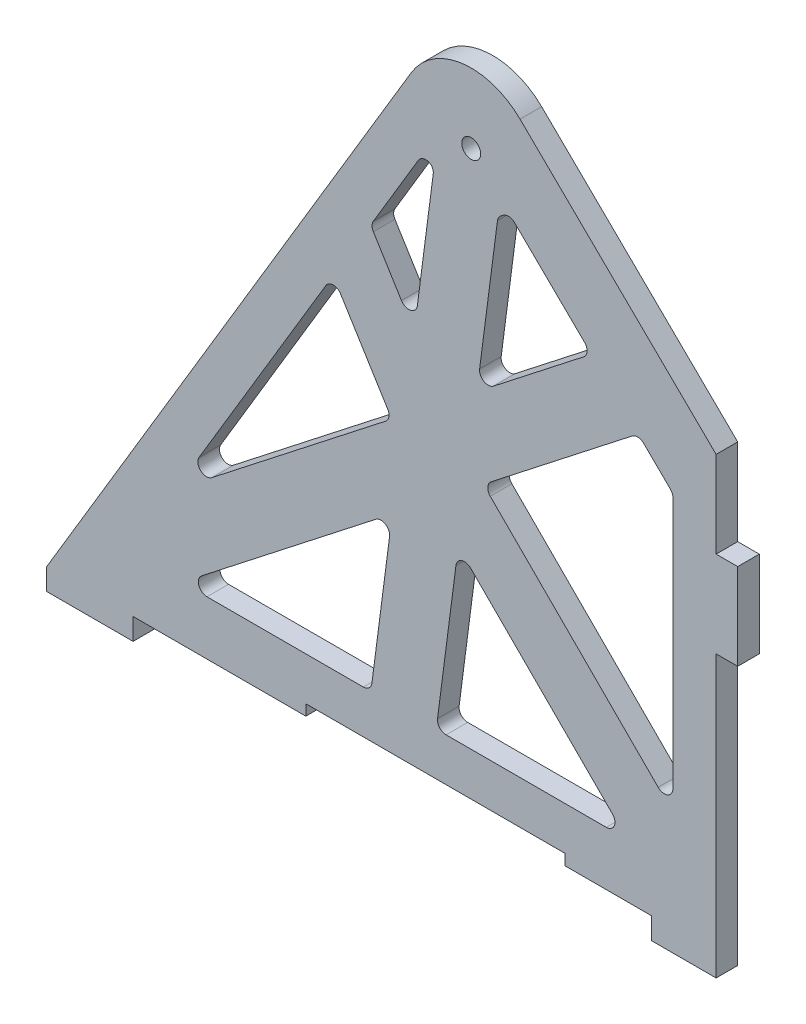
SolidWorks part; units mm, degrees
ref_plane "Front Plane" through (0, 0, 0) normal (0, 0, 1) x (1, 0, 0)
ref_plane "Top Plane" through (0, 0, 0) normal (0, 1, 0) x (1, 0, 0)
ref_plane "Right Plane" through (0, 0, 0) normal (1, 0, 0) x (0, 0, -1)
sketch "Sketch2" plane through (0, 0, 0) normal (0, 0, 1) x (1, 0, 0)
  line L0 (0, 2.5421) -> (203.2, 2.5421) construction
  line L1 (25.4, 2.5421) -> (76.2, 2.5421)
  line L2 (0, 2.5421) -> (107.2144, 181.9515)
  line L4 (76.2, 2.5421) -> (76.2, 5.7171)
  line L6 (0, 2.5421) -> (0, -3.8079)
  line L7 (0, -3.8079) -> (25.4, -3.8079)
  line L8 (25.4, 2.5421) -> (25.4, -3.8079)
  line L13 (76.2, 5.7171) -> (152.4, 5.7171)
  line L14 (152.4, 5.7171) -> (152.4, 2.5421)
  line L16 (152.4, 2.5421) -> (177.8, 2.5421)
  line L17 (0, -33.6061) -> (203.2, -33.6061) construction
  line L18 (177.8, 2.5421) -> (177.8, -3.8079)
  line L19 (177.8, -3.8079) -> (196.85, -3.8079)
  line L20 (196.85, -3.8079) -> (196.85, 78.7421)
  line L22 (196.85, 129.5421) -> (139.2046, 186.0765)
  line L23 (196.85, 104.1421) -> (196.85, 129.5421)
  line L24 (196.85, 104.1421) -> (203.2, 104.1421)
  line L26 (196.85, 78.7421) -> (203.2, 78.7421)
  line L27 (203.2, 104.1421) -> (203.2, 78.7421)
  arc A0 (139.2046, 186.0765) -> (107.2144, 181.9515) centre (124.8331, 171.4226) ccw
  circle A1 centre (124.8331, 171.4226) radius 11 construction
  circle A2 centre (124.8331, 171.4226) radius 4 construction
  circle A3 centre (124.8331, 171.4226) radius 2.7781
  dimension "D3" = 22
  dimension "D4" = 9.525
  dimension "D5" = 8
  dimension "D6" = 5.5562
  dimension "D1" = 168.8805
  dimension "D2" = 124.8331
  dimension "D7" = 6.35
  dimension "D8" = 25.4
  dimension "D9" = 19.05
  dimension "D10" = 6.35
  dimension "D11" = 44.45
  dimension "D12" = 203.2
  dimension "D13" = 76.2
  dimension "D14" = 3.175
  dimension "D15" = 133.35
  dimension "D16" = 6.35
  dimension "D17" = 25.4
  dimension "D18" = 25.4
extrude "Boss-Extrude1" add sketch "Sketch2" along normal blind 6.35
sketch "Sketch4" plane through (0, 0, 6.35) normal (0, 0, 1) x (1, 0, 0)
  line L0 (111.2656, 163.9732) -> (10.9017, -3.9728)
  line L1 (124.8331, 171.4226) -> (184.15, 113.2489)
  line L2 (118.1161, 175.4367) -> (10.9017, -3.9728) construction
  line L3 (24.2818, 18.4171) -> (184.15, 18.4171)
  line L4 (124.8331, 171.4226) -> (103.2992, 5.7171) construction
  line L5 (134.2787, 170.1951) -> (112.7448, 4.4896)
  line L6 (115.3875, 172.6501) -> (93.8537, 6.9445)
  line L7 (24.2818, 18.4171) -> (114.0662, 88.5698) construction
  line L8 (18.4173, 25.9226) -> (108.2017, 96.0754)
  line L9 (30.1462, 10.9115) -> (119.9306, 81.0643)
  line L10 (114.0662, 88.5698) -> (89.7368, 127.9475) construction
  line L11 (105.9631, 83.5633) -> (81.6336, 122.9409)
  line L12 (122.1693, 93.5763) -> (97.8399, 132.954)
  line L13 (0, 2.5421) -> (0, -3.8079)
  line L14 (0, -3.8079) -> (25.4, -3.8079)
  line L15 (25.4, -3.8079) -> (25.4, 2.5421)
  line L16 (25.4, 2.5421) -> (76.2, 2.5421)
  line L17 (76.2, 2.5421) -> (76.2, 5.7171)
  line L18 (76.2, 5.7171) -> (152.4, 5.7171)
  line L19 (152.4, 5.7171) -> (152.4, 2.5421)
  line L20 (152.4, 2.5421) -> (177.8, 2.5421)
  line L21 (177.8, -3.8079) -> (196.85, -3.8079)
  line L22 (177.8, 2.5421) -> (177.8, -3.8079)
  line L23 (152.4, 2.5421) -> (177.8, 2.5421)
  line L24 (196.85, -3.8079) -> (196.85, 78.7421)
  line L25 (107.2144, 181.9515) -> (0, 2.5421)
  line L26 (0, 2.5421) -> (0, -3.8079)
  line L27 (0, -3.8079) -> (25.4, -3.8079)
  line L28 (25.4, -3.8079) -> (25.4, 2.5421)
  line L29 (25.4, 2.5421) -> (76.2, 2.5421)
  line L30 (76.2, 2.5421) -> (76.2, 5.7171)
  line L31 (76.2, 5.7171) -> (152.4, 5.7171)
  line L32 (152.4, 5.7171) -> (152.4, 2.5421)
  line L34 (177.8, -3.8079) -> (196.85, -3.8079)
  line L35 (177.8, 2.5421) -> (177.8, -3.8079)
  line L38 (107.2144, 181.9515) -> (0, 2.5421)
  line L39 (114.0662, 88.5698) -> (172.0162, 133.8489) construction
  line L40 (108.2017, 96.0754) -> (166.1517, 141.3545)
  line L41 (119.9306, 81.0643) -> (177.8807, 126.3433)
  line L42 (114.0662, 88.5698) -> (184.15, 18.4171) construction
  line L43 (120.8047, 95.3017) -> (190.8885, 25.1489)
  line L44 (107.3277, 81.838) -> (177.4115, 11.6852)
  line L45 (97.8399, 132.954) -> (84.7663, 154.1138)
  line L46 (166.1517, 141.3545) -> (164.1076, 139.7573)
  line L47 (184.15, 113.2489) -> (184.15, 18.4171)
  line L60 (196.85, -3.8079) -> (196.85, 78.7421)
  line L61 (196.85, 129.5421) -> (139.2046, 186.0765)
  line L62 (196.85, 129.5421) -> (139.2046, 186.0765)
  line L68 (196.85, 78.7421) -> (203.2, 78.7421)
  line L69 (196.85, 78.7421) -> (203.2, 78.7421)
  line L70 (203.2, 78.7421) -> (203.2, 104.1421)
  line L71 (203.2, 78.7421) -> (203.2, 104.1421)
  line L72 (203.2, 104.1421) -> (196.85, 104.1421)
  line L73 (203.2, 104.1421) -> (196.85, 104.1421)
  line L74 (196.85, 104.1421) -> (196.85, 129.5421)
  line L75 (196.85, 104.1421) -> (196.85, 129.5421)
  arc A0 (134.2787, 170.1951) -> (115.3875, 172.6501) centre (124.8331, 171.4226) ccw
  arc A1 (139.2046, 186.0765) -> (107.2144, 181.9515) centre (124.8331, 171.4226) ccw
  arc A2 (139.2046, 186.0765) -> (107.2144, 181.9515) centre (124.8331, 171.4226) ccw
  arc A3 (93.8537, 6.9445) -> (112.7448, 4.4896) centre (103.2992, 5.7171) ccw
  circle A4 centre (124.8331, 171.4226) radius 15.4781
  circle A5 centre (124.8331, 171.4226) radius 15.4781
  arc A6 (18.4173, 25.9226) -> (30.1462, 10.9115) centre (24.2818, 18.4171) ccw
  arc A7 (119.9306, 81.0643) -> (108.2017, 96.0754) centre (114.0662, 88.5698) ccw
  arc A8 (105.9631, 83.5633) -> (122.1693, 93.5763) centre (114.0662, 88.5698) ccw
  arc A9 (97.8399, 132.954) -> (81.6336, 122.9409) centre (89.7368, 127.9475) ccw
  arc A10 (108.2017, 96.0754) -> (119.9306, 81.0643) centre (114.0662, 88.5698) ccw
  arc A11 (177.8807, 126.3433) -> (166.1517, 141.3545) centre (172.0162, 133.8489) ccw
  arc A12 (120.8047, 95.3017) -> (107.3277, 81.838) centre (114.0662, 88.5698) ccw
  arc A13 (177.4115, 11.6852) -> (190.8885, 25.1489) centre (184.15, 18.4171) ccw
  point P15 (171.6589, 134.3025)
  point P18 (114.0662, 88.5698)
  point P31 (69.174, 53.4934)
  point P39 (101.9015, 108.2586)
  point P44 (143.0412, 111.2094)
  point P51 (149.1081, 53.4934)
  dimension "D6" = 9.525
  dimension "D4" = 12.7
  dimension "D5" = 12.7
  dimension "D1" = 0
  dimension "D2" = 12.7
  dimension "D3" = 12.7
extrude "Cut-Extrude1" cut sketch "Sketch4" against normal through all contours A5 L0 L45 L12 L6 | A5 L5 L40 L46 | L41 L43 | L44 L5 L3 | L9 L3 L6 | L8 L11 L0 region at (105.8659, 140.4246, 6.35) region at (140.0823, 136.4968, 6.35) region at (74.5143, 83.5502, 6.35) region at (165.0491, 82.2709, 6.35) region at (78.908, 34.5324, 6.35) region at (135.4189, 34.9901, 6.35)
fillet "Fillet1" radius 2.54 21 edges at (101.6272, 66.7629, 3.175) (95.3445, 18.4171, 3.175) (39.7522, 18.4171, 3.175) (128.4096, 87.6893, 3.175) (113.8153, 160.5515, 3.175) (108.076, 116.3867, 3.175) (111.2656, 163.9732, 3.175) (84.2318, 118.7357, 3.175) (101.4783, 90.8221, 3.175) (37.8327, 41.0928, 3.175) (132.7065, 158.0966, 3.175) (170.6862, 18.4171, 3.175) (114.5547, 18.4171, 3.175) (121.0159, 68.1363, 3.175) (95.2417, 137.1592, 3.175) (135.8838, 160.5849, 3.175) (160.2189, 136.7188, 3.175) (126.5051, 110.3767, 3.175) (184.15, 31.8941, 3.175) (173.9388, 123.2633, 3.175) (184.15, 113.2489, 3.175)
